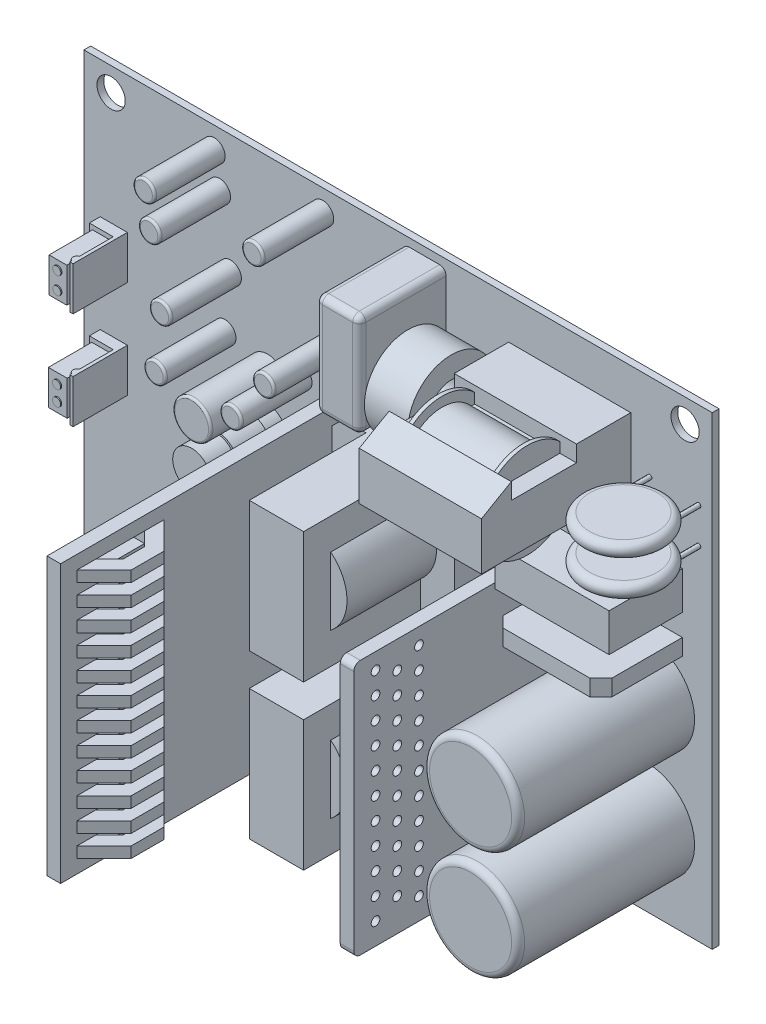
SolidWorks part; units mm, degrees
material "PW50:34:C1:0:1:2:Re:16:"
ref_plane "Front" through (0, 0, 0) normal (0, 0, 1) x (1, 0, 0)
ref_plane "Top" through (0, 0, 0) normal (0, 1, 0) x (1, 0, 0)
ref_plane "Side" through (0, 0, 0) normal (1, 0, 0) x (0, 0, -1)
sketch "Sketch1" plane through (0, 0, 0) normal (0, 0, 1) x (1, 0, 0)
  line L0 (-73.4695, 40.132) -> (-73.4695, -68.58)
  line L2 (-73.4695, -68.58) -> (73.4695, -68.58)
  line L4 (-73.4695, 40.132) -> (73.4695, 40.132)
  line L5 (73.4695, 40.132) -> (73.4695, -68.58)
  circle A3 centre (67.1195, 34.6075) radius 3.302
  circle A5 centre (-67.1195, 34.6075) radius 3.302
extrude "Base-Extrude" add sketch "Sketch1" along normal blind 1.5875
sketch "Sketch3" plane through (0, 0, 1.5875) normal (0, 0, 1) x (1, 0, 0)
  line L0 (73.4695, 40.132) -> (73.4695, -68.58) construction
  line L1 (-73.4695, -68.58) -> (73.4695, -68.58) construction
  circle A0 centre (58.2295, -49.53) radius 11.1125
  circle A1 centre (58.2295, -24.13) radius 11.1125
  dimension "D1" = 22.225
  dimension "D4" = 25.4
  dimension "D2" = 15.24
  dimension "D3" = 19.05
extrude "Boss-Extrude1" add sketch "Sketch3" along normal blind 41.275
fillet "Fillet1" radius 1.524 2 edges at (69.342, -24.13, 42.8625) (69.342, -49.53, 42.8625)
sketch "Sketch4" plane through (0, 0, 1.5875) normal (0, 0, 1) x (1, 0, 0)
  line L0 (66.4845, -8.89) -> (41.0845, -8.89)
  line L1 (66.4845, -8.89) -> (66.4845, -12.7)
  line L2 (41.0845, -12.7) -> (66.4845, -12.7)
  line L3 (41.0845, -12.7) -> (41.0845, -8.89)
  line L4 (-73.4695, -68.58) -> (73.4695, -68.58) construction
  line L5 (73.4695, 40.132) -> (73.4695, -68.58) construction
  dimension "D1" = 25.4
  dimension "D2" = 3.81
  dimension "D3" = 59.69
  dimension "D4" = 6.985
extrude "Boss-Extrude2" add sketch "Sketch4" along normal blind 19.05
chamfer "Chamfer1" distance 2.54 angle 45 2 edges at (66.4845, -10.795, 20.6375) (41.0845, -10.795, 20.6375)
sketch "Sketch5" plane through (0, 0, 1.5875) normal (0, 0, 1) x (1, 0, 0)
  line L0 (39.8145, 5.08) -> (66.4845, 5.08)
  line L1 (39.8145, 5.08) -> (39.8145, -3.81)
  line L2 (66.4845, -3.81) -> (39.8145, -3.81)
  line L3 (66.4845, -3.81) -> (66.4845, 5.08)
  line L4 (-73.4695, -68.58) -> (73.4695, -68.58) construction
  line L5 (73.4695, 40.132) -> (73.4695, -68.58) construction
  dimension "D1" = 26.67
  dimension "D2" = 8.89
  dimension "D3" = 73.66
  dimension "D4" = 6.985
extrude "Boss-Extrude3" add sketch "Sketch5" along normal blind 17.145
ref_plane "Plane4" through (0, 19.812, 0) normal (0, 1, 0) x (-1, 0, 0)
sketch "Sketch6" plane through (0, 19.812, 0) normal (0, 1, 0) x (-1, 0, 0)
  line L0 (-64.5795, -2.54) -> (-64.5795, 29.21) construction
  line L2 (-70.2945, 1.5875) -> (-70.2945, 6.7362)
  line L3 (-58.8645, 1.5875) -> (-58.8645, 6.7362)
  line L6 (73.4695, 1.5875) -> (-73.4695, 1.5875) construction
  arc A0 (-58.2116, 8.7074) -> (-70.9474, 8.7074) centre (-64.5795, 13.4459) ccw
  arc A1 (-58.2116, 8.7074) -> (-58.8645, 6.7362) centre (-55.5625, 6.7362) ccw
  arc A2 (-70.9474, 8.7074) -> (-70.2945, 6.7362) centre (-73.5965, 6.7362) cw
  point P13 (-58.8645, 7.9375)
  dimension "D4" = 3.302
  dimension "D5" = 5.715
  dimension "D6" = 8.89
  dimension "D3" = 7.9375
  dimension "D1" = 5.1487
  dimension "D2" = 11.8584
sketch "Sketch7" plane through (0, 0, 1.5875) normal (0, 0, 1) x (1, 0, 0)
  circle A0 centre (70.2945, 19.812) radius 0.508
  dimension "D1" = 1.016
sweep "Boss-Sweep1" add profiles "Sketch7" path "Sketch6"
ref_plane "Plane5" through (0, 0, 13.4493) normal (0, 0, 1) x (1, 0, 0)
sketch "Sketch8" plane through (0, 0, 13.4493) normal (0, 0, 1) x (1, 0, 0)
  line L0 (73.4695, 40.132) -> (73.4695, -68.58) construction
  line L1 (-73.4695, 40.132) -> (73.4695, 40.132) construction
  line L2 (72.4493, 21.463) -> (64.5795, 21.463)
  line L3 (64.5795, 19.812) -> (64.5795, 13.7195) construction
  line L4 (64.5795, 21.463) -> (64.5795, 18.161)
  line L5 (72.4493, 18.161) -> (64.5795, 18.161)
  arc A0 (72.4493, 18.161) -> (72.4493, 21.463) centre (72.4493, 19.812) ccw
  dimension "D1" = 3.302
  dimension "D2" = 20.32
  dimension "D3" = 1.0202
  dimension "D4" = 8.89
revolve "Boss-Revolve1" add sketch "Sketch8" angle 360 about L3
pattern_linear "LPattern1" count 2 spacing 8.255 along (0, -1, 0) of "Boss-Revolve1", "Boss-Sweep1"
sketch "Sketch9" plane through (0, 0, 1.5875) normal (0, 0, 1) x (1, 0, 0)
  line L0 (25.8445, 30.607) -> (54.4195, 30.607)
  line L1 (25.8445, 30.607) -> (25.8445, 11.557)
  line L2 (54.4195, 11.557) -> (25.8445, 11.557)
  line L3 (54.4195, 11.557) -> (54.4195, 30.607)
  line L4 (-73.4695, 40.132) -> (73.4695, 40.132) construction
  line L5 (73.4695, 40.132) -> (73.4695, -68.58) construction
  dimension "D1" = 28.575
  dimension "D2" = 19.05
  dimension "D3" = 9.525
  dimension "D4" = 19.05
extrude "Boss-Extrude4" add sketch "Sketch9" along normal blind 34.925
sketch "Sketch10" plane through (54.4195, 0, 0) normal (1, 0, 0) x (0, 0, -1)
  line L0 (-29.5275, 30.607) -> (-42.1593, 23.314)
  line L1 (-14.2875, 40.132) -> (-14.2875, -68.58)
  line L2 (-14.2875, 40.132) -> (-14.2875, 26.797)
  line L3 (-29.5275, 40.132) -> (-29.5275, -68.58)
  line L4 (-29.5275, 30.607) -> (-29.5275, 26.797)
  line L5 (-36.5125, 15.367) -> (-1.5875, 15.367)
  line L6 (-42.1593, 15.367) -> (-14.2875, 15.367)
  line L7 (-36.5125, 26.797) -> (-1.5875, 26.797)
  line L8 (-29.5275, 26.797) -> (-14.2875, 26.797)
  line L9 (-36.5125, 30.607) -> (-1.5875, 30.607) construction
  line L10 (-14.2875, 7.4511) -> (-47.8412, 7.4511)
  line L11 (-47.8412, 7.4511) -> (-47.8412, 40.132)
  line L12 (-47.8412, 40.132) -> (-14.2875, 40.132)
  line L13 (-14.2875, 15.367) -> (-14.2875, 7.4511)
  line L14 (-42.1593, 23.314) -> (-42.1593, 15.367)
  dimension "D5" = 27.8718
  dimension "D6" = 33.5537
  dimension "D7" = 32.6809
  dimension "D8" = 30
  dimension "D1" = 12.7
  dimension "D2" = 27.94
  dimension "D3" = 3.81
  dimension "D4" = 3.81
extrude "Cut-Extrude1" cut sketch "Sketch10" against normal through all
ref_plane "Plane6" through (54.4195, 0, 0) normal (-1, 0, 0) x (0, 0, 1)
ref_plane "Plane7" through (40.132, 0, 0) normal (-1, 0, 0) x (0, 0, 1)
sketch "Sketch11" plane through (40.132, 0, 0) normal (-1, 0, 0) x (0, 0, 1)
  line L0 (14.2875, 15.367) -> (14.2875, 26.797) construction
  line L1 (14.2875, 21.082) -> (29.5275, 21.082) construction
  line L3 (29.5275, 30.607) -> (29.5275, 26.797) construction
  circle A0 centre (21.9075, 21.082) radius 8.89
  dimension "D1" = 17.78
extrude "Boss-Extrude5" add sketch "Sketch11" along normal mid plane 19.05
sketch "Sketch12" plane through (49.657, 0, 0) normal (1, 0, 0) x (0, 0, -1)
  circle A0 centre (-21.9075, 21.082) radius 11.1125
  dimension "D1" = 22.225
extrude "Boss-Extrude6" add sketch "Sketch12" along normal blind 0.889
sketch "Sketch13" plane through (30.607, 0, 0) normal (-1, 0, 0) x (0, 0, 1)
  circle A0 centre (21.9075, 21.082) radius 11.1125
  arc A1 (29.5275, 29.1705) -> (14.2875, 29.1705) centre (21.9075, 21.082) ccw construction
extrude "Boss-Extrude7" add sketch "Sketch13" along normal blind 0.889
ref_plane "Plane8" through (17.272, 0, 0) normal (-1, 0, 0) x (0, 0, 1)
sketch "Sketch14" plane through (17.272, 0, 0) normal (-1, 0, 0) x (0, 0, 1)
  line L0 (21.9075, 21.082) -> (15.647, 21.082) construction
  line L1 (1.5875, 40.132) -> (1.5875, -68.58) construction
  circle A0 centre (11.4935, 21.082) radius 10.16
  circle A1 centre (11.4935, 21.082) radius 5.08
  dimension "D1" = 20.32
  dimension "D2" = 10.16
  dimension "D3" = 9.906
extrude "Boss-Extrude8" add sketch "Sketch14" along normal mid plane 10.16
sketch "Sketch15" plane through (0, 0, 1.5875) normal (0, 0, 1) x (1, 0, 0)
  line L0 (2.6035, 14.097) -> (9.7155, 14.097)
  line L1 (1.0795, 15.621) -> (1.0795, 36.703)
  line L2 (9.7155, 38.227) -> (2.6035, 38.227)
  line L3 (11.2395, 36.703) -> (11.2395, 15.621)
  line L4 (73.4695, 40.132) -> (73.4695, -68.58) construction
  line L5 (-73.4695, 40.132) -> (73.4695, 40.132) construction
  arc A0 (1.0795, 15.621) -> (2.6035, 14.097) centre (2.6035, 15.621) ccw
  arc A1 (11.2395, 15.621) -> (9.7155, 14.097) centre (9.7155, 15.621) cw
  arc A2 (11.2395, 36.703) -> (9.7155, 38.227) centre (9.7155, 36.703) ccw
  arc A3 (2.6035, 38.227) -> (1.0795, 36.703) centre (2.6035, 36.703) ccw
  dimension "D5" = 1.524
  dimension "D1" = 62.23
  dimension "D2" = 10.16
  dimension "D3" = 1.905
  dimension "D4" = 24.13
extrude "Boss-Extrude9" add sketch "Sketch15" along normal blind 20.32
fillet "Fillet2" radius 1.524 8 edges at (1.0795, 26.162, 21.9075) (1.5259, 37.7806, 21.9075) (1.5259, 14.5434, 21.9075) (6.1595, 38.227, 21.9075) (6.1595, 14.097, 21.9075) (10.7931, 37.7806, 21.9075) (10.7931, 14.5434, 21.9075) (11.2395, 26.162, 21.9075)
sketch "Sketch16" plane through (0, 0, 1.5875) normal (0, 0, 1) x (1, 0, 0)
  line L0 (33.4645, -5.715) -> (36.6395, -5.715)
  line L1 (33.4645, -5.715) -> (33.4645, -65.405)
  line L2 (36.6395, -65.405) -> (33.4645, -65.405)
  line L3 (36.6395, -65.405) -> (36.6395, -5.715)
  line L4 (73.4695, 40.132) -> (73.4695, -68.58) construction
  line L5 (-73.4695, -68.58) -> (73.4695, -68.58) construction
  dimension "D1" = 36.83
  dimension "D2" = 3.175
  dimension "D3" = 3.175
  dimension "D4" = 59.69
extrude "Boss-Extrude10" add sketch "Sketch16" along normal blind 46.99
fillet "Fillet3" radius 1.524 2 edges at (35.052, -65.405, 48.5775) (35.052, -5.715, 48.5775)
sketch "Sketch17" plane through (36.6395, 0, 0) normal (1, 0, 0) x (0, 0, -1)
  line L0 (-48.5775, -63.881) -> (-48.5775, -7.239) construction
  line L1 (-47.0535, -65.405) -> (-1.5875, -65.405) construction
  circle A0 centre (-43.4975, -60.325) radius 1.016
  circle A2 centre (-33.3375, -60.325) radius 1.016
  dimension "D1" = 2.032
  dimension "D2" = 5.08
  dimension "D3" = 5.08
  dimension "D4" = 10.16
extrude "Cut-Extrude2" cut sketch "Sketch17" against normal through all
pattern_linear "LPattern2" count 11 spacing 5.08 along (0, 1, 0) of "Cut-Extrude2"
sketch "Sketch18" plane through (36.6395, 0, 0) normal (1, 0, 0) x (0, 0, -1)
  circle A0 centre (-38.4175, -57.785) radius 1.016
  circle A1 centre (-43.4975, -60.325) radius 1.016 construction
  circle A2 centre (-43.4975, -55.245) radius 1.016 construction
  dimension "D1" = 5.08
  dimension "D2" = 2.54
extrude "Cut-Extrude3" cut sketch "Sketch18" against normal through all
pattern_linear "LPattern3" count 10 spacing 5.08 along (0, 1, 0) of "Cut-Extrude3"
sketch "Sketch19" plane through (0, 0, 1.5875) normal (0, 0, 1) x (1, 0, 0)
  line L0 (-3.3655, -33.02) -> (20.1295, -33.02)
  line L1 (-5.9055, -35.56) -> (-5.9055, -60.96)
  line L2 (20.1295, -63.5) -> (-3.3655, -63.5)
  line L3 (22.6695, -60.96) -> (22.6695, -35.56)
  line L4 (73.4695, 40.132) -> (73.4695, -68.58) construction
  line L5 (-73.4695, -68.58) -> (73.4695, -68.58) construction
  line L6 (-3.3655, -33.02) -> (-5.9055, -35.56)
  line L9 (-5.9055, -60.96) -> (-3.3655, -63.5)
  line L11 (20.1295, -63.5) -> (22.6695, -60.96)
  line L13 (22.6695, -35.56) -> (20.1295, -33.02)
  dimension "D1" = 135
  dimension "D2" = 45
  dimension "D3" = 135
  dimension "D4" = 135
  dimension "D5" = 28.575
  dimension "D6" = 30.48
  dimension "D7" = 2.54
  dimension "D8" = 50.8
  dimension "D9" = 5.08
extrude "Boss-Extrude11" add sketch "Sketch19" along normal blind 36.83
sketch "Sketch20" plane through (0, 0, 38.4175) normal (0, 0, 1) x (1, 0, 0)
  line L0 (22.6695, -48.26) -> (-5.9055, -48.26) construction
  line L3 (22.6695, -60.96) -> (22.6695, -35.56) construction
  line L4 (-5.9055, -35.56) -> (-5.9055, -60.96) construction
  line L5 (8.382, -48.26) -> (8.382, -24.765) construction
  line L6 (33.4645, -24.765) -> (36.6395, -24.765) construction
  line L7 (2.032, -29.21) -> (2.032, -40.3289)
  line L9 (14.732, -29.21) -> (14.732, -40.3289)
  line L10 (2.032, -29.21) -> (-4.9437, -29.21)
  line L11 (2.032, -56.1911) -> (2.032, -67.31)
  line L12 (14.732, -56.1911) -> (14.732, -67.31)
  line L13 (14.732, -67.31) -> (21.7077, -67.31)
  line L18 (-4.9437, -29.21) -> (-9.7155, -33.9818)
  line L19 (-9.7155, -33.9818) -> (-9.7155, -62.5382)
  line L20 (-9.7155, -62.5382) -> (-4.9437, -67.31)
  line L21 (-4.9437, -67.31) -> (21.7077, -67.31)
  line L22 (21.7077, -67.31) -> (26.4795, -62.5382)
  line L23 (26.4795, -62.5382) -> (26.4795, -33.9818)
  line L24 (26.4795, -33.9818) -> (21.7077, -29.21)
  line L25 (21.7077, -29.21) -> (-4.9437, -29.21)
  line L26 (-4.9437, -29.21) -> (-9.7155, -33.9818)
  line L27 (-9.7155, -33.9818) -> (-9.7155, -62.5382)
  line L28 (-9.7155, -62.5382) -> (-4.9437, -67.31)
  line L29 (-4.9437, -67.31) -> (2.032, -67.31)
  line L30 (21.7077, -67.31) -> (26.4795, -62.5382)
  line L31 (26.4795, -62.5382) -> (26.4795, -33.9818)
  line L32 (26.4795, -33.9818) -> (21.7077, -29.21)
  line L33 (21.7077, -29.21) -> (14.732, -29.21)
  arc A0 (2.032, -40.3289) -> (2.032, -56.1911) centre (8.382, -48.26) ccw
  arc A1 (14.732, -56.1911) -> (14.732, -40.3289) centre (8.382, -48.26) ccw
  dimension "D2" = 20.32
  dimension "D1" = 12.7
  dimension "D3" = 3.81
extrude "Cut-Extrude4" cut sketch "Sketch20" against normal offset from surface (27.305 mm away) 9.525 up to face at (35.052, -35.56, 1.5875)
sketch "Sketch21" plane through (0, 0, 38.4175) normal (0, 0, 1) x (1, 0, 0)
  line L0 (2.032, -33.02) -> (2.032, -40.3289) construction
  line L1 (2.032, -37.3547) -> (2.032, -59.1653)
  line L2 (14.732, -33.02) -> (14.732, -40.3289) construction
  line L3 (14.732, -37.3547) -> (14.732, -59.1653)
  line L4 (-0.3493, -37.3547) -> (2.032, -37.3547)
  line L5 (-0.3493, -59.1653) -> (2.032, -59.1653)
  line L6 (14.732, -37.3547) -> (17.1132, -37.3547)
  line L7 (14.732, -59.1653) -> (17.1132, -59.1653)
  arc A1 (17.1132, -59.1653) -> (17.1132, -37.3547) centre (8.382, -48.26) ccw
  arc A2 (17.1132, -59.1653) -> (17.1132, -37.3547) centre (8.382, -48.26) ccw
  arc A3 (-0.3493, -37.3547) -> (-0.3493, -59.1653) centre (8.382, -48.26) ccw
  arc A4 (-0.3493, -37.3547) -> (-0.3493, -59.1653) centre (8.382, -48.26) ccw
  dimension "D1" = 3.81
  dimension "D2" = 3.81
extrude "Cut-Extrude5" cut sketch "Sketch21" against normal blind 6.35
pattern_linear "LPattern4" count 2 spacing 38.1 along (0, 1, 0) of "Cut-Extrude5", "Cut-Extrude4", "Boss-Extrude11"
sketch "Sketch22" plane through (0, 0, 1.5875) normal (0, 0, 1) x (1, 0, 0)
  line L0 (-16.0655, -0.635) -> (-12.8905, -0.635)
  line L1 (-16.0655, -0.635) -> (-16.0655, -65.405)
  line L2 (-12.8905, -65.405) -> (-16.0655, -65.405)
  line L3 (-12.8905, -65.405) -> (-12.8905, -0.635)
  line L4 (-73.4695, -68.58) -> (73.4695, -68.58) construction
  line L5 (73.4695, 40.132) -> (73.4695, -68.58) construction
  dimension "D1" = 3.175
  dimension "D2" = 3.175
  dimension "D3" = 64.77
  dimension "D4" = 86.36
extrude "Boss-Extrude12" add sketch "Sketch22" along normal blind 66.04
sketch "Sketch23" plane through (0, -0.635, 0) normal (0, 1, 0) x (-1, 0, 0)
  line L0 (12.8905, 63.8175) -> (6.5405, 57.4675)
  line L1 (12.8905, 67.6275) -> (12.8905, 1.5875) construction
  line L2 (6.5405, 57.4675) -> (6.5405, 49.8475)
  line L3 (6.5405, 49.8475) -> (12.8905, 43.4975)
  line L4 (12.8905, 47.9876) -> (9.7155, 51.1626)
  line L5 (9.7155, 51.1626) -> (9.7155, 56.1524)
  line L6 (9.7155, 56.1524) -> (12.8905, 59.3274)
  line L7 (12.8905, 59.3274) -> (12.8905, 63.8175)
  line L8 (12.8905, 47.9876) -> (12.8905, 43.4975)
  line L9 (16.0655, 67.6275) -> (12.8905, 67.6275) construction
  dimension "D1" = 3.175
  dimension "D2" = 3.175
  dimension "D3" = 135
  dimension "D4" = 135
  dimension "D5" = 3.175
  dimension "D6" = 3.175
  dimension "D7" = 3.81
  dimension "D8" = 20.32
extrude "Boss-Extrude13" add sketch "Sketch23" against normal up to surface (64.77 mm away) up to face at (-14.478, -65.405, 34.6075)
sketch "Sketch24" plane through (0, 0, 67.6275) normal (0, 0, 1) x (1, 0, 0)
  line L2 (-16.1074, -32.385) -> (-48.09, -32.385) construction
  line L4 (-12.8905, -19.05) -> (-12.8905, -16.51)
  line L5 (-12.8905, -24.13) -> (-12.8905, -21.59)
  line L6 (-12.8905, -8.89) -> (-6.2865, -8.89)
  line L8 (-12.8905, -29.21) -> (-12.8905, -26.67)
  line L9 (-6.2865, -69.85) -> (-6.2865, -62.23)
  line L10 (-12.8905, -69.85) -> (-12.8905, -62.23)
  line L11 (-12.8905, -34.29) -> (-12.8905, -31.75)
  line L12 (-12.8905, -6.35) -> (-6.2865, -6.35)
  line L13 (-12.8905, -11.43) -> (-6.2865, -11.43)
  line L14 (-12.8905, -13.97) -> (-6.2865, -13.97)
  line L15 (-12.8905, -16.51) -> (-6.2865, -16.51)
  line L16 (-12.8905, -19.05) -> (-6.2865, -19.05)
  line L17 (-6.2865, -8.89) -> (-6.2865, -6.35)
  line L18 (-12.8905, -8.89) -> (-12.8905, -6.35)
  line L19 (-12.8905, -13.97) -> (-12.8905, -11.43)
  line L20 (-6.2865, -13.97) -> (-6.2865, -11.43)
  line L21 (-12.8905, -21.59) -> (-6.2865, -21.59)
  line L22 (-12.8905, -24.13) -> (-6.2865, -24.13)
  line L23 (-12.8905, -26.67) -> (-6.2865, -26.67)
  line L25 (-12.8905, -29.21) -> (-6.2865, -29.21)
  line L26 (-12.8905, -31.75) -> (-6.2865, -31.75)
  line L27 (-12.8905, -34.29) -> (-6.2865, -34.29)
  line L29 (-12.8905, -36.83) -> (-6.2865, -36.83)
  line L30 (-12.8905, -39.37) -> (-6.2865, -39.37)
  line L31 (-12.8905, -41.91) -> (-6.2865, -41.91)
  line L33 (-12.8905, -44.45) -> (-6.2865, -44.45)
  line L34 (-12.8905, -46.99) -> (-6.2865, -46.99)
  line L36 (-12.8905, -49.53) -> (-6.2865, -49.53)
  line L38 (-12.8905, -52.07) -> (-6.2865, -52.07)
  line L39 (-12.8905, -54.61) -> (-6.2865, -54.61)
  line L40 (-12.8905, -57.15) -> (-6.2865, -57.15)
  line L41 (-12.8905, -39.37) -> (-12.8905, -36.83)
  line L42 (-12.8905, -44.45) -> (-12.8905, -41.91)
  line L43 (-12.8905, -49.53) -> (-12.8905, -46.99)
  line L44 (-12.8905, -54.61) -> (-12.8905, -52.07)
  line L45 (-6.2865, -54.61) -> (-6.2865, -52.07)
  line L46 (-6.2865, -49.53) -> (-6.2865, -46.99)
  line L47 (-6.2865, -44.45) -> (-6.2865, -41.91)
  line L48 (-6.2865, -39.37) -> (-6.2865, -36.83)
  line L49 (-6.2865, -34.29) -> (-6.2865, -31.75)
  line L50 (-6.2865, -29.21) -> (-6.2865, -26.67)
  line L51 (-6.2865, -24.13) -> (-6.2865, -21.59)
  line L52 (-6.2865, -19.05) -> (-6.2865, -16.51)
  line L53 (-6.2865, -59.69) -> (-12.8905, -59.69)
  line L55 (-6.2865, -62.23) -> (-12.8905, -62.23)
  line L57 (-6.2865, -69.85) -> (-12.8905, -69.85)
  line L61 (-6.2865, -59.69) -> (-6.2865, -57.15)
  line L62 (-12.8905, -59.69) -> (-12.8905, -57.15)
  line L63 (-12.8905, -65.405) -> (-12.8905, -0.635) construction
  line L64 (-12.8905, -65.405) -> (-6.5405, -65.405) construction
  line L65 (-12.8905, -3.81) -> (-6.2865, -3.81)
  line L67 (-12.8905, -3.81) -> (-12.8905, -0.381)
  line L68 (-12.8905, -0.381) -> (-6.5405, -0.381)
  line L69 (-12.8905, -0.381) -> (-6.2865, -0.381)
  line L70 (-6.2865, -3.81) -> (-6.2865, -0.381)
  line L71 (-16.0655, -0.635) -> (-12.8905, -0.635) construction
  dimension "D2" = 2.54
  dimension "D4" = 2.54
  dimension "D5" = 2.54
  dimension "D6" = 2.54
  dimension "D7" = 2.54
  dimension "D8" = 2.54
  dimension "D9" = 2.54
  dimension "D10" = 2.54
  dimension "D11" = 2.54
  dimension "D12" = 2.54
  dimension "D13" = 2.54
  dimension "D14" = 2.54
  dimension "D15" = 2.54
  dimension "D16" = 2.54
  dimension "D17" = 2.54
  dimension "D18" = 2.54
  dimension "D1" = 2.54
  dimension "D3" = 2.54
  dimension "D19" = 2.54
  dimension "D20" = 2.54
  dimension "D21" = 63.5
  dimension "D22" = 3.175
  dimension "D23" = 2.54
  dimension "D24" = 2.54
  dimension "D25" = 6.604
  dimension "D26" = 2.54
  dimension "D27" = 0.254
  dimension "D28" = 3.175
extrude "Cut-Extrude6" cut sketch "Sketch24" against normal blind 25.4
sketch "Sketch25" plane through (-16.0655, 0, 0) normal (-1, 0, 0) x (0, 0, 1)
  line L0 (56.1524, -62.23) -> (51.1626, -62.23) construction
  line L1 (56.1524, -59.69) -> (51.1626, -59.69) construction
  line L2 (51.1626, -57.15) -> (56.1524, -57.15) construction
  line L3 (51.1626, -54.61) -> (56.1524, -54.61) construction
  line L4 (51.1626, -52.07) -> (56.1524, -52.07) construction
  line L5 (51.1626, -49.53) -> (56.1524, -49.53) construction
  line L6 (51.1626, -46.99) -> (56.1524, -46.99) construction
  line L7 (51.1626, -44.45) -> (56.1524, -44.45) construction
  line L8 (51.1626, -41.91) -> (56.1524, -41.91) construction
  line L9 (51.1626, -39.37) -> (56.1524, -39.37) construction
  line L10 (51.1626, -36.83) -> (56.1524, -36.83) construction
  line L11 (51.1626, -34.29) -> (56.1524, -34.29) construction
  line L12 (51.1626, -31.75) -> (56.1524, -31.75) construction
  line L13 (51.1626, -29.21) -> (56.1524, -29.21) construction
  line L14 (51.1626, -26.67) -> (56.1524, -26.67) construction
  line L15 (51.1626, -24.13) -> (56.1524, -24.13) construction
  line L16 (51.1626, -21.59) -> (56.1524, -21.59) construction
  line L17 (51.1626, -19.05) -> (56.1524, -19.05) construction
  line L18 (51.1626, -16.51) -> (56.1524, -16.51) construction
  line L19 (51.1626, -13.97) -> (56.1524, -13.97) construction
  line L20 (51.1626, -11.43) -> (56.1524, -11.43) construction
  line L21 (51.1626, -8.89) -> (56.1524, -8.89) construction
  line L22 (51.1626, -3.81) -> (56.1524, -3.81) construction
  line L23 (51.1626, -6.35) -> (56.1524, -6.35) construction
  line L24 (59.3274, -62.23) -> (47.9876, -62.23)
  line L25 (59.3274, -59.69) -> (47.9876, -59.69)
  line L26 (47.9876, -57.15) -> (59.3274, -57.15)
  line L27 (47.9876, -54.61) -> (59.3274, -54.61)
  line L28 (47.9876, -52.07) -> (59.3274, -52.07)
  line L29 (47.9876, -49.53) -> (59.3274, -49.53)
  line L30 (47.9876, -46.99) -> (59.3274, -46.99)
  line L31 (47.9876, -44.45) -> (59.3274, -44.45)
  line L32 (47.9876, -41.91) -> (59.3274, -41.91)
  line L33 (47.9876, -39.37) -> (59.3274, -39.37)
  line L34 (47.9876, -36.83) -> (59.3274, -36.83)
  line L35 (47.9876, -34.29) -> (59.3274, -34.29)
  line L36 (47.9876, -31.75) -> (59.3274, -31.75)
  line L37 (47.9876, -29.21) -> (59.3274, -29.21)
  line L38 (47.9876, -26.67) -> (59.3274, -26.67)
  line L39 (47.9876, -24.13) -> (59.3274, -24.13)
  line L40 (47.9876, -21.59) -> (59.3274, -21.59)
  line L41 (47.9876, -19.05) -> (59.3274, -19.05)
  line L42 (47.9876, -16.51) -> (59.3274, -16.51)
  line L43 (47.9876, -13.97) -> (59.3274, -13.97)
  line L44 (47.9876, -11.43) -> (59.3274, -11.43)
  line L45 (47.9876, -8.89) -> (59.3274, -8.89)
  line L46 (47.9876, -3.81) -> (59.3274, -3.81)
  line L47 (47.9876, -6.35) -> (59.3274, -6.35)
  line L48 (47.9876, -6.35) -> (47.9876, -3.81) construction
  line L49 (47.9876, -62.23) -> (47.9876, -59.69)
  line L50 (59.3274, -6.35) -> (59.3274, -3.81) construction
  line L51 (59.3274, -62.23) -> (59.3274, -59.69)
  line L52 (43.4975, -62.23) -> (47.9876, -62.23) construction
  line L53 (59.3274, -62.23) -> (63.8175, -62.23) construction
  line L54 (59.3274, -57.15) -> (59.3274, -54.61)
  line L55 (59.3274, -46.99) -> (59.3274, -44.45)
  line L56 (59.3274, -41.91) -> (59.3274, -39.37)
  line L57 (59.3274, -36.83) -> (59.3274, -34.29)
  line L58 (59.3274, -31.75) -> (59.3274, -29.21)
  line L59 (59.3274, -26.67) -> (59.3274, -24.13)
  line L60 (59.3274, -21.59) -> (59.3274, -19.05)
  line L61 (59.3274, -16.51) -> (59.3274, -13.97)
  line L62 (59.3274, -11.43) -> (59.3274, -8.89)
  line L63 (59.3274, -6.35) -> (59.3274, -3.81)
  line L64 (47.9876, -6.35) -> (47.9876, -3.81)
  line L65 (47.9876, -11.43) -> (47.9876, -8.89)
  line L66 (47.9876, -16.51) -> (47.9876, -13.97)
  line L67 (47.9876, -21.59) -> (47.9876, -19.05)
  line L68 (47.9876, -26.67) -> (47.9876, -24.13)
  line L69 (47.9876, -31.75) -> (47.9876, -29.21)
  line L70 (47.9876, -36.83) -> (47.9876, -34.29)
  line L71 (47.9876, -41.91) -> (47.9876, -39.37)
  line L72 (47.9876, -46.99) -> (47.9876, -44.45)
  line L73 (47.9876, -52.07) -> (47.9876, -49.53)
  line L74 (47.9876, -57.15) -> (47.9876, -54.61)
  line L75 (59.3274, -52.07) -> (59.3274, -49.53)
extrude "Cut-Extrude7" cut sketch "Sketch25" against normal up to next
sketch "Sketch26" plane through (-16.0655, 0, 0) normal (-1, 0, 0) x (0, 0, 1)
  line L0 (9.2075, -10.795) -> (29.5275, -10.795)
  line L1 (1.5875, -12.065) -> (1.5875, -14.605)
  line L2 (29.5275, -26.035) -> (9.2075, -26.035)
  line L3 (29.5275, -26.035) -> (29.5275, -10.795)
  line L4 (1.5875, -24.765) -> (9.2075, -24.765)
  line L5 (1.5875, -14.605) -> (9.2075, -14.605)
  line L6 (1.5875, -12.065) -> (9.2075, -12.065)
  line L7 (9.2075, -17.145) -> (1.5875, -17.145)
  line L8 (9.2075, -17.145) -> (9.2075, -14.605)
  line L9 (1.5875, -19.685) -> (9.2075, -19.685)
  line L10 (1.5875, -22.225) -> (1.5875, -24.765)
  line L11 (9.2075, -22.225) -> (1.5875, -22.225)
  line L12 (9.2075, -26.035) -> (9.2075, -24.765)
  line L13 (1.5875, -17.145) -> (1.5875, -19.685)
  line L14 (9.2075, -12.065) -> (9.2075, -10.795)
  line L15 (9.2075, -22.225) -> (9.2075, -19.685)
  line L16 (1.5875, 40.132) -> (1.5875, -68.58) construction
  line L17 (67.6275, -0.635) -> (1.5875, -0.635) construction
  line L18 (67.6275, -33.02) -> (105.41, -33.02) construction
  line L19 (67.6275, -0.635) -> (67.6275, -65.405) construction
  line L20 (9.2075, -43.815) -> (9.2075, -46.355)
  line L21 (9.2075, -53.975) -> (9.2075, -55.245)
  line L22 (1.5875, -48.895) -> (1.5875, -46.355)
  line L23 (9.2075, -40.005) -> (9.2075, -41.275)
  line L24 (9.2075, -43.815) -> (1.5875, -43.815)
  line L25 (1.5875, -43.815) -> (1.5875, -41.275)
  line L26 (1.5875, -46.355) -> (9.2075, -46.355)
  line L27 (9.2075, -48.895) -> (9.2075, -51.435)
  line L28 (9.2075, -48.895) -> (1.5875, -48.895)
  line L29 (1.5875, -53.975) -> (9.2075, -53.975)
  line L30 (1.5875, -51.435) -> (9.2075, -51.435)
  line L31 (1.5875, -41.275) -> (9.2075, -41.275)
  line L32 (29.5275, -40.005) -> (29.5275, -55.245)
  line L33 (29.5275, -40.005) -> (9.2075, -40.005)
  line L34 (1.5875, -53.975) -> (1.5875, -51.435)
  line L35 (9.2075, -55.245) -> (29.5275, -55.245)
  dimension "D1" = 15.24
  dimension "D2" = 2.54
  dimension "D3" = 2.54
  dimension "D4" = 2.54
  dimension "D5" = 2.54
  dimension "D6" = 2.54
  dimension "D7" = 1.27
  dimension "D8" = 27.94
  dimension "D9" = 7.62
  dimension "D10" = 10.16
extrude "Boss-Extrude14" add sketch "Sketch26" along normal blind 1.524
sketch "Sketch27" plane through (-17.5895, 0, 0) normal (-1, 0, 0) x (0, 0, 1)
  line L0 (9.2075, -10.795) -> (29.5275, -10.795) construction
  line L1 (9.4615, -22.225) -> (9.4615, -19.685)
  line L2 (9.4615, -55.245) -> (9.4615, -40.005)
  line L3 (24.4475, -26.035) -> (24.4475, -10.795)
  line L4 (24.4475, -55.245) -> (24.4475, -40.005)
  line L5 (9.4615, -10.795) -> (24.4475, -10.795)
  line L6 (29.5275, -26.035) -> (9.2075, -26.035) construction
  line L7 (24.4475, -26.035) -> (9.4615, -26.035)
  line L8 (29.5275, -40.005) -> (9.2075, -40.005) construction
  line L9 (24.4475, -40.005) -> (9.4615, -40.005)
  line L10 (9.2075, -55.245) -> (29.5275, -55.245) construction
  line L11 (9.4615, -55.245) -> (24.4475, -55.245)
  line L12 (24.4475, -26.035) -> (24.4475, -10.795)
  line L13 (9.4615, -26.035) -> (9.4615, -10.795)
  dimension "D1" = 0.254
  dimension "D2" = 5.08
extrude "Boss-Extrude15" add sketch "Sketch27" along normal blind 2.54
ref_plane "Plane9" through (0, 0, 13.462) normal (0, 0, 1) x (1, 0, 0)
sketch "Sketch28" plane through (0, 0, 13.462) normal (0, 0, 1) x (1, 0, 0)
  line L0 (-12.8905, -33.02) -> (-50.8, -33.02) construction
  line L1 (-12.8905, -65.405) -> (-12.8905, -0.635) construction
  line L2 (-33.3712, -39.878) -> (-26.2255, -39.878)
  line L3 (-36.6732, -43.18) -> (-36.6732, -43.434)
  line L4 (-26.2255, -46.736) -> (-33.3712, -46.736)
  line L5 (-22.9235, -43.434) -> (-22.9235, -43.18)
  line L6 (-16.0655, -0.635) -> (-16.0655, -65.405) construction
  arc A0 (-22.9235, -43.434) -> (-26.2255, -46.736) centre (-26.2255, -43.434) cw
  arc A1 (-33.3712, -46.736) -> (-36.6732, -43.434) centre (-33.3712, -43.434) cw
  arc A2 (-22.9235, -43.18) -> (-26.2255, -39.878) centre (-26.2255, -43.18) ccw
  arc A3 (-36.6732, -43.18) -> (-33.3712, -39.878) centre (-33.3712, -43.18) cw
  dimension "D1" = 3.302
  dimension "D3" = 3.302
  dimension "D4" = 7.1457
  dimension "D5" = 10.16
  dimension "D2" = 6.858
  dimension "D6" = 13.716
revolve "Boss-Revolve2" add sketch "Sketch28" angle 360 about L0
sketch "Sketch29" plane through (0, 0, 1.5875) normal (0, 0, 1) x (1, 0, 0)
  line L0 (-16.0655, -0.635) -> (-12.8905, -0.635) construction
  line L1 (73.4695, 40.132) -> (73.4695, -68.58) construction
  line L2 (-73.4695, 40.132) -> (-73.4695, -68.58) construction
  line L3 (-73.4695, 40.132) -> (73.4695, 40.132) construction
  circle A0 centre (-42.9895, 35.052) radius 2.54
  circle A1 centre (-41.7195, 27.432) radius 2.54
  circle A2 centre (-17.5895, 35.052) radius 2.54
  circle A3 centre (-15.0495, 9.652) radius 2.54
  circle A4 centre (-39.1795, 12.192) radius 2.54
  circle A5 centre (-40.4495, -0.508) radius 2.54
  circle A6 centre (-22.6695, -0.635) radius 2.54
  dimension "D1" = 5.08
  dimension "D3" = 30.48
  dimension "D4" = 31.75
  dimension "D5" = 34.29
  dimension "D6" = 33.02
  dimension "D7" = 50.8
  dimension "D2" = 91.059
  dimension "D8" = 58.42
  dimension "D9" = 5.08
  dimension "D10" = 12.7
  dimension "D11" = 27.94
  dimension "D12" = 30.48
  dimension "D13" = 40.64
extrude "Boss-Extrude16" add sketch "Sketch29" along normal blind 16.51
fillet "Fillet4" radius 0.508 7 edges at (-20.1295, -0.635, 18.0975) (-37.9095, -0.508, 18.0975) (-36.6395, 12.192, 18.0975) (-15.0495, 35.052, 18.0975) (-39.1795, 27.432, 18.0975) (-40.4495, 35.052, 18.0975) (-12.5095, 9.652, 18.0975)
sketch "Sketch30" plane through (0, 0, 1.5875) normal (0, 0, 1) x (1, 0, 0)
  line L0 (33.4645, -14.605) -> (36.6395, -14.605) construction
  line L1 (-73.4695, 40.132) -> (73.4695, 40.132) construction
  line L2 (-73.4695, 40.132) -> (-73.4695, -68.58) construction
  circle A0 centre (-30.48, -4.445) radius 4.445
  circle A1 centre (-30.48, -14.605) radius 4.445
  dimension "D1" = 8.89
  dimension "D2" = 10.16
  dimension "D3" = 44.577
  dimension "D4" = 42.9895
extrude "Boss-Extrude17" add sketch "Sketch30" along normal blind 17.78
fillet "Fillet5" radius 0.508 1 edges at (-26.035, -4.445, 19.3675)
sketch "Sketch31" plane through (0, 0, 13.462) normal (0, 0, 1) x (1, 0, 0)
  circle A1 centre (-30.48, -14.605) radius 4.953
  circle A2 centre (-30.48, -14.605) radius 4.953
  dimension "D1" = 0.508
extrude "Boss-Extrude22" add sketch "Sketch31" against normal blind 7.62
sketch "Sketch32" plane through (0, 0, 1.5875) normal (0, 0, 1) x (1, 0, 0)
  line L0 (33.4645, -57.785) -> (36.6395, -57.785) construction
  line L1 (33.4645, -45.085) -> (36.6395, -45.085) construction
  line L2 (-73.4695, -68.58) -> (73.4695, -68.58) construction
  line L3 (-73.4695, 40.132) -> (-73.4695, -68.58) construction
  circle A0 centre (-31.5595, -57.785) radius 6.35
  circle A1 centre (-50.6095, -45.085) radius 6.35
  dimension "D1" = 12.7
  dimension "D2" = 10.795
  dimension "D3" = 41.91
  dimension "D4" = 22.86
  dimension "D5" = 23.495
extrude "Boss-Extrude23" add sketch "Sketch32" along normal blind 20.32
fillet "Fillet6" radius 0.762 2 edges at (-44.2595, -45.085, 21.9075) (-25.2095, -57.785, 21.9075)
sketch "Sketch33" plane through (0, 0, 1.5875) normal (0, 0, 1) x (1, 0, 0)
  line L0 (-69.6595, -14.605) -> (-63.3095, -14.605)
  line L1 (-69.6595, -14.605) -> (-69.6595, -24.765)
  line L2 (-63.3095, -24.765) -> (-69.6595, -24.765)
  line L3 (-63.3095, -24.765) -> (-63.3095, -14.605)
  line L7 (-73.4695, 40.132) -> (-73.4695, -68.58) construction
  line L8 (-73.4695, 40.132) -> (73.4695, 40.132) construction
  dimension "D1" = 10.16
  dimension "D2" = 6.35
  dimension "D3" = 3.81
  dimension "D4" = 54.737
extrude "Boss-Extrude24" add sketch "Sketch33" along normal blind 12.7
sketch "Sketch34" plane through (0, -14.605, 0) normal (0, 1, 0) x (-1, 0, 0)
  line L0 (69.6595, 14.2875) -> (63.3095, 14.2875) construction
  line L1 (73.4695, 4.1275) -> (-73.4695, 4.1275)
  line L2 (70.4215, 4.1275) -> (64.0715, 4.1275)
  line L3 (64.0715, 14.2875) -> (64.0715, 1.5875)
  line L4 (64.0715, 15.0495) -> (64.0715, 13.8354)
  line L5 (64.0715, 12.0443) -> (64.0715, 4.1275)
  line L6 (70.4215, 15.0495) -> (63.3095, 15.0495)
  line L7 (70.4215, 15.0495) -> (70.4215, 1.5875)
  line L8 (70.4215, 15.0495) -> (64.0715, 15.0495)
  line L9 (70.4215, 15.0495) -> (70.4215, 4.1275)
  arc A0 (64.0715, 12.0443) -> (64.0715, 13.8354) centre (63.7415, 12.9399) ccw
  dimension "D4" = 0.9544
  dimension "D5" = 1.3476
  dimension "D6" = 0.33
  dimension "D1" = 2.54
  dimension "D2" = 0.762
  dimension "D3" = 0.762
extrude "Cut-Extrude8" cut sketch "Sketch34" against normal blind 12.7
sketch "Sketch35" plane through (0, 0, 4.1275) normal (0, 0, 1) x (1, 0, 0)
  line L0 (-69.6595, -19.685) -> (-59.0894, -19.685) construction
  line L2 (-69.6595, -14.605) -> (-69.6595, -24.765) construction
  line L3 (-68.1355, -16.891) -> (-66.6115, -16.891)
  line L4 (-68.1355, -16.891) -> (-68.1355, -18.415)
  line L5 (-66.6115, -18.415) -> (-68.1355, -18.415)
  line L6 (-66.6115, -18.415) -> (-66.6115, -16.891)
  line L7 (-68.1355, -22.479) -> (-66.6115, -22.479)
  line L8 (-68.1355, -22.479) -> (-68.1355, -20.955)
  line L9 (-66.6115, -20.955) -> (-68.1355, -20.955)
  line L10 (-66.6115, -20.955) -> (-66.6115, -22.479)
  dimension "D1" = 1.524
  dimension "D2" = 1.524
  dimension "D3" = 5.588
extrude "Boss-Extrude25" add sketch "Sketch35" along normal blind 8.89
sketch "Sketch36" plane through (0, 0, 4.1275) normal (0, 0, 1) x (1, 0, 0)
  line L0 (-64.6724, -15.621) -> (-69.088, -15.621)
  line L1 (-64.6724, -15.621) -> (-64.6724, -23.749)
  line L2 (-69.088, -23.749) -> (-64.6724, -23.749)
  line L3 (-69.088, -23.749) -> (-69.088, -22.479)
  line L4 (-69.088, -16.891) -> (-66.6115, -16.891)
  line L6 (-66.6115, -22.479) -> (-69.088, -22.479)
  line L7 (-66.6115, -22.479) -> (-66.6115, -16.891)
  line L8 (-68.1355, -22.479) -> (-66.6115, -22.479) construction
  line L9 (-68.1355, -16.891) -> (-66.6115, -16.891) construction
  line L10 (-69.088, -16.891) -> (-69.088, -15.621)
  dimension "D1" = 1.27
  dimension "D2" = 1.27
extrude "Boss-Extrude26" add sketch "Sketch36" along normal up to surface (8.89 mm away) up to face at (-67.3735, -17.653, 13.0175)
sketch "Sketch37" plane through (0, 0, 13.0175) normal (0, 0, 1) x (1, 0, 0)
  line L0 (-64.6927, -15.621) -> (-69.088, -15.621)
  line L1 (-64.6927, -15.621) -> (-64.6927, -23.749)
  line L2 (-69.088, -23.749) -> (-64.6927, -23.749)
  line L3 (-69.088, -23.749) -> (-69.088, -15.621)
extrude "Boss-Extrude27" add sketch "Sketch37" along normal blind 1.27
sketch "Sketch38" plane through (0, 0, 14.2875) normal (0, 0, 1) x (1, 0, 0)
  line L0 (-69.088, -19.685) -> (-65.3313, -19.685) construction
  line L1 (-69.088, -23.749) -> (-69.088, -15.621) construction
  circle A0 centre (-66.9276, -17.9163) radius 0.9525
  circle A1 centre (-66.9276, -21.4537) radius 0.9525
  dimension "D1" = 1.905
extrude "Boss-Extrude28" add sketch "Sketch38" along normal blind 0.254
ref_plane "Plane10" through (-66.9276, 0, 0) normal (-1, 0, 0) x (0, 0, 1)
pattern_linear "LPattern8" count 2 spacing 22.86 along (0, 1, 0) of "Boss-Extrude25", "Cut-Extrude8", "Boss-Extrude24"
sketch "Sketch47" plane through (0, 0, 4.1275) normal (0, 0, 1) x (1, 0, 0)
  line L0 (-64.77, 7.239) -> (-68.9243, 7.239)
  line L1 (-64.77, 7.239) -> (-64.77, -0.889)
  line L2 (-68.9243, -0.889) -> (-64.77, -0.889)
  line L3 (-68.9243, -0.889) -> (-68.9243, 0.381)
  line L4 (-68.9243, 5.969) -> (-66.6115, 5.969)
  line L6 (-66.6115, 0.381) -> (-68.9243, 0.381)
  line L7 (-66.6115, 0.381) -> (-66.6115, 5.969)
  line L8 (-68.9243, 5.969) -> (-68.9243, 7.239)
  dimension "D1" = 1.27
  dimension "D2" = 1.27
extrude "Boss-Extrude29" add sketch "Sketch47" along normal up to surface (8.89 mm away) up to face at (-67.3735, 5.207, 13.0175)
sketch "Sketch48" plane through (0, 0, 13.0175) normal (0, 0, 1) x (1, 0, 0)
  line L0 (-64.77, 7.239) -> (-68.9243, 7.239)
  line L1 (-64.77, 7.239) -> (-64.77, -0.889)
  line L2 (-68.9243, -0.889) -> (-64.77, -0.889)
  line L3 (-68.9243, -0.889) -> (-68.9243, 7.239)
extrude "Boss-Extrude30" add sketch "Sketch48" along normal blind 1.27
sketch "Sketch51" plane through (0, 0, 14.2875) normal (0, 0, 1) x (1, 0, 0)
  line L0 (-68.9243, 3.175) -> (-66.1467, 3.175) construction
  line L1 (-68.9243, -0.889) -> (-68.9243, 7.239) construction
  circle A0 centre (-66.8706, 5.2042) radius 0.9525
  circle A1 centre (-66.8706, 1.1458) radius 0.9525
  dimension "D1" = 1.905
extrude "Boss-Extrude31" add sketch "Sketch51" along normal blind 0.254
scale "Scale1" scale about centroid uniform scaling yes scale factor 0.6
